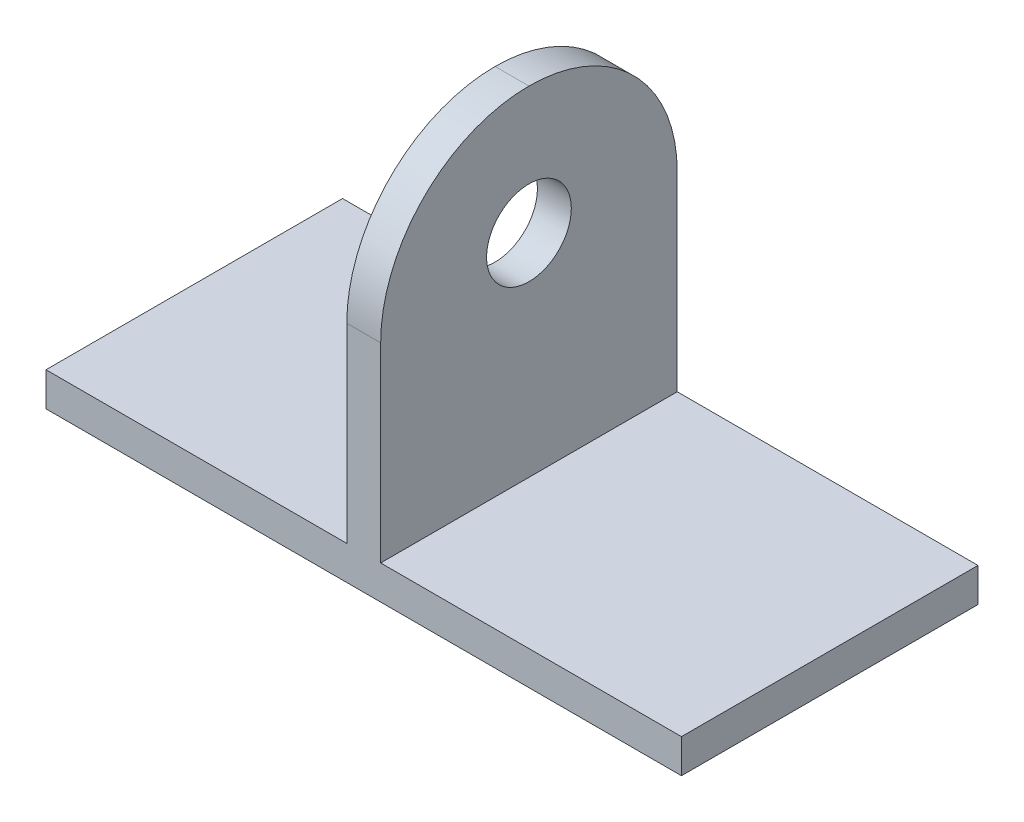
SolidWorks part; units mm, degrees
ref_plane "Front Plane" through (0, 0, 0) normal (0, 0, 1) x (1, 0, 0)
ref_plane "Top Plane" through (0, 0, 0) normal (0, 1, 0) x (1, 0, 0)
ref_plane "Right Plane" through (0, 0, 0) normal (1, 0, 0) x (0, 0, -1)
sketch "Sketch1" plane through (0, 0, 0) normal (0, 1, 0) x (1, 0, 0)
  line L1 (37.5, -17.5) -> (-37.5, -17.5)
  line L2 (37.5, -17.5) -> (37.5, 17.5)
  line L3 (37.5, 17.5) -> (-37.5, 17.5)
  line L4 (-37.5, -17.5) -> (-37.5, 17.5)
  line L5 (37.5, -17.5) -> (-37.5, 17.5) construction
  line L6 (37.5, 17.5) -> (-37.5, -17.5) construction
  point P0 (0, 0)
  dimension "D1" = 35
  dimension "D2" = 75
extrude "Boss-Extrude1" add sketch "Sketch1" along normal blind 4
sketch "Sketch2" plane through (0, 4, 0) normal (0, 1, 0) x (1, 0, 0)
  line L0 (37.5, 17.5) -> (-37.5, 17.5) construction
  line L1 (2, -17.5) -> (-2, -17.5)
  line L2 (2, -17.5) -> (2, 17.5)
  line L3 (2, 17.5) -> (-2, 17.5)
  line L4 (-2, -17.5) -> (-2, 17.5)
  line L5 (2, -17.5) -> (-2, 17.5) construction
  line L6 (2, 17.5) -> (-2, -17.5) construction
  point P0 (0, 0)
  dimension "D1" = 4
extrude "Boss-Extrude2" add sketch "Sketch2" along normal blind 40
sketch "Sketch3" plane through (2, 0, 0) normal (1, 0, 0) x (0, 0, -1)
  line L0 (-17.5, 4) -> (17.5, 4) construction
  circle A0 centre (0, 29) radius 5
  dimension "D1" = 10
  dimension "D2" = 25
extrude "Cut-Extrude1" cut sketch "Sketch3" against normal through all
fillet "Fillet1" radius 17.5 2 edges at (0, 44, -17.5) (0, 44, 17.5)
